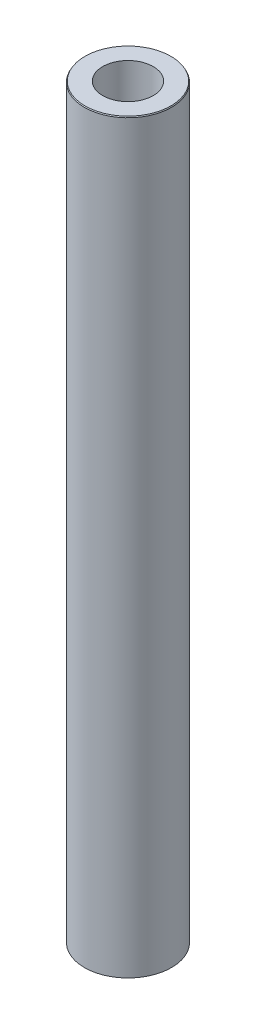
SolidWorks part; units mm, degrees
ref_plane "Front Plane" through (0, 0, 0) normal (0, 0, 1) x (1, 0, 0)
ref_plane "Top Plane" through (0, 0, 0) normal (0, 1, 0) x (1, 0, 0)
ref_plane "Right Plane" through (0, 0, 0) normal (1, 0, 0) x (0, 0, -1)
sketch "Sketch1" plane through (0, 0, 0) normal (0, 1, 0) x (1, 0, 0)
  circle A0 centre (0, 0) radius 35
  dimension "SHAFT_OD" = 70
extrude "Boss-Extrude1" add sketch "Sketch1" along normal blind 600
sketch "Sketch2" plane through (0, 0, 0) normal (0, 1, 0) x (1, 0, 0)
  circle A0 centre (0, 0) radius 20.2749
  dimension "BORE_D" = 40.5497
extrude "Cut-Extrude1" cut sketch "Sketch2" along normal through all
chamfer "Chamfer1" distance 0.8028 angle 30 2 edges at (0, 600, 35) (0, 0, 35) first distance on face at (0, 600, 35) first distance on face at (0, 0, 20.2749)
